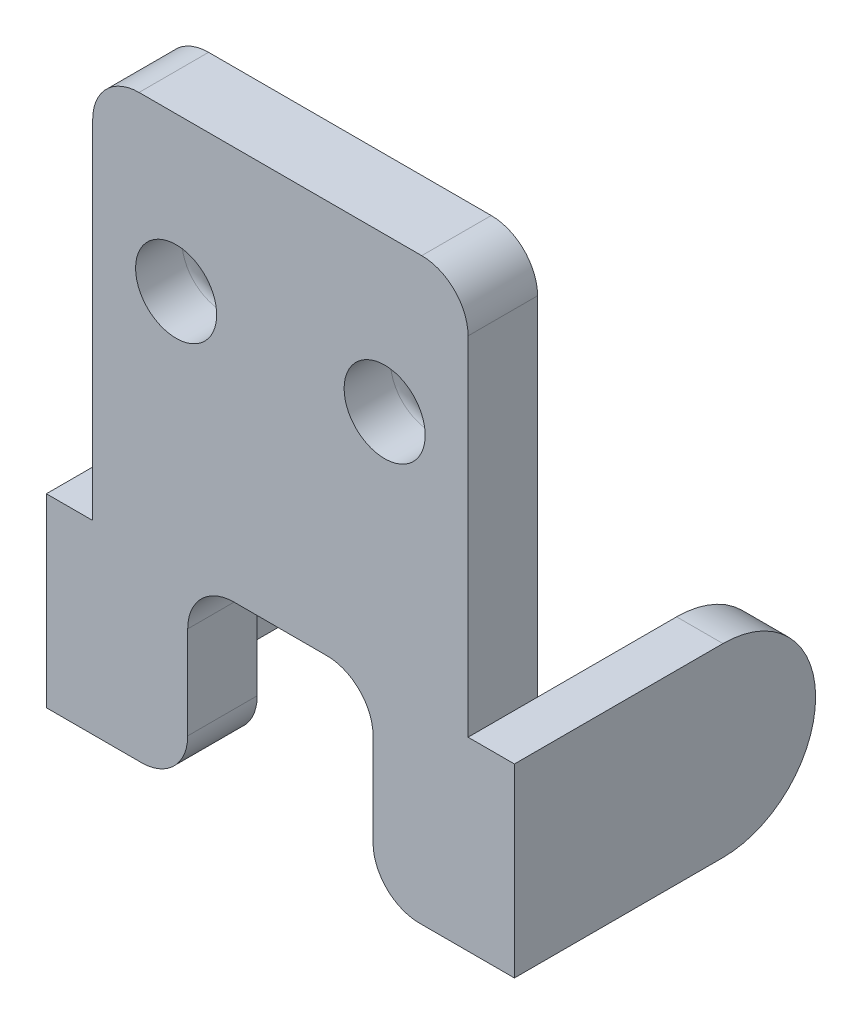
SolidWorks part; units mm, degrees
ref_plane "Plan de face" through (0, 0, 0) normal (0, 0, 1) x (1, 0, 0)
ref_plane "Plan de dessus" through (0, 0, 0) normal (0, 1, 0) x (1, 0, 0)
ref_plane "Plan de droite" through (0, 0, 0) normal (1, 0, 0) x (0, 0, -1)
sketch "Esquisse1" plane through (0, 0, 0) normal (0, 0, 1) x (1, 0, 0)
  line L1 (0, 0) -> (16.2, 0)
  line L2 (0, 0) -> (0, 25)
  line L3 (0, 25) -> (16.2, 25)
  line L4 (16.2, 0) -> (16.2, 25)
  dimension "D1" = 16.2
  dimension "D2" = 25
extrude "Boss.-Extru.1" add sketch "Esquisse1" along normal blind 3
sketch "Esquisse2" plane through (0, 0, 0) normal (-1, 0, 0) x (0, 0, 1)
  line L0 (0, 25) -> (0, 0) construction
  line L1 (3, 0) -> (-10, 0)
  line L2 (3, 0) -> (3, 8)
  line L3 (3, 8) -> (-10, 8)
  line L4 (-10, 0) -> (-10, 8)
  dimension "D1" = 8
  dimension "D2" = 10
extrude "Boss.-Extru.2" add sketch "Esquisse2" along normal blind 2
sketch "Esquisse3" plane through (0, 0, 0) normal (1, 0, 0) x (0, 0, -1)
  line L0 (0, 8) -> (0, 0) construction
  circle A0 centre (7, 4.0358) radius 1.8
  dimension "D1" = 3.6
  dimension "D2" = 7
extrude "Boss.-Extru.3" add sketch "Esquisse3" along normal blind 1.5
sketch "Esquisse5" plane through (16.2, 0, 0) normal (1, 0, 0) x (0, 0, -1)
  line L0 (0, 0) -> (0, 25) construction
  line L1 (-3, 0) -> (10, 0)
  line L2 (-3, 0) -> (-3, 8)
  line L3 (-3, 8) -> (10, 8)
  line L4 (10, 0) -> (10, 8)
  dimension "D1" = 10
  dimension "D2" = 8
extrude "Boss.-Extru.4" add sketch "Esquisse5" along normal blind 2
sketch "Esquisse6" plane through (16.2, 0, 0) normal (-1, 0, 0) x (0, 0, 1)
  line L0 (0, 8) -> (0, 25) construction
  circle A0 centre (-7, 3.8797) radius 1.8
  point P4 (0, 16.5)
  dimension "D1" = 3.6
  dimension "D2" = 7
extrude "Boss.-Extru.5" add sketch "Esquisse6" along normal blind 1.5
sketch "Esquisse7" plane through (0, 0, 0) normal (0, 0, -1) x (-1, 0, 0)
  line L0 (0, 0) -> (-16.2, 0) construction
  line L1 (-12.1, 0) -> (-4.1, 0)
  line L2 (-12.1, 0) -> (-12.1, 8)
  line L3 (-12.1, 8) -> (-4.1, 8)
  line L4 (-4.1, 0) -> (-4.1, 8)
  line L5 (-16.2, 25) -> (0, 25) construction
  point P6 (-8.1, 25)
  point P9 (-8.1, 8)
  dimension "D1" = 0
  dimension "D2" = 8
  dimension "D3" = 8
extrude "Enlèv. mat.-Extru.1" cut sketch "Esquisse7" against normal up to next
sketch "Esquisse8" plane through (0, 0, 0) normal (0, 0, -1) x (-1, 0, 0)
  line L0 (-16.2, 25) -> (0, 25) construction
  circle A0 centre (-12.6, 18.3601) radius 1.75
  circle A1 centre (-3.6, 18.3601) radius 1.75
  point P6 (-8.1, 25)
  dimension "D1" = 3.5
  dimension "D2" = 3.5
  dimension "D3" = 4.5
  dimension "D4" = 4.5
extrude "Enlèv. mat.-Extru.2" cut sketch "Esquisse8" against normal up to next
fillet "Congé1" radius 1 2 edges at (1.85, 18.3601, 0) (10.85, 18.3601, 0)
fillet "Congé2" radius 4 4 edges at (-1, 8, -10) (-1, 0, -10) (17.2, 8, -10) (17.2, 0, -10)
fillet "Congé3" radius 2 4 edges at (4.1, 0, 1.5) (4.1, 8, 1.5) (12.1, 8, 1.5) (12.1, 0, 1.5)
fillet "Congé4" radius 2 2 edges at (0, 25, 1.5) (16.2, 25, 1.5)
